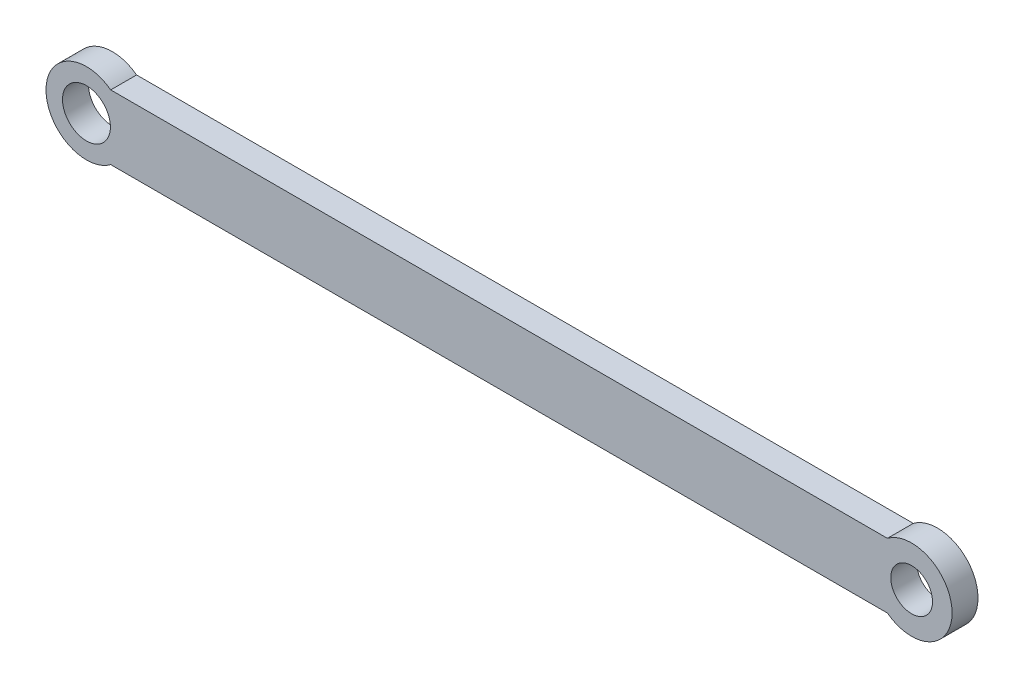
SolidWorks part; units mm, degrees
ref_plane "Front Plane" through (0, 0, 0) normal (0, 0, 1) x (1, 0, 0)
ref_plane "Top Plane" through (0, 0, 0) normal (0, 1, 0) x (1, 0, 0)
ref_plane "Right Plane" through (0, 0, 0) normal (1, 0, 0) x (0, 0, -1)
sketch "Sketch1" plane through (0, 0, 0) normal (0, 0, 1) x (1, 0, 0)
  line L1 (4.7625, 0) -> (157.1625, 0)
  line L3 (4.7625, 12.7) -> (157.1625, 12.7)
  arc A0 (4.7625, 12.7) -> (4.7625, 0) centre (0, 6.35) ccw
  arc A1 (157.1625, 0) -> (157.1625, 12.7) centre (161.925, 6.35) ccw
  dimension "D3" = 15.875
  dimension "D4" = 15.875
extrude "Boss-Extrude1" add sketch "Sketch1" along normal blind 5.08
sketch "Sketch2" plane through (0, 0, 0) normal (0, 0, -1) x (-1, 0, 0)
  circle A0 centre (-161.925, 6.35) radius 4.0958
  arc A1 (-157.1625, 12.7) -> (-157.1625, 0) centre (-161.925, 6.35) ccw construction
  circle A2 centre (0, 6.35) radius 4.699
  arc A3 (-4.7625, 0) -> (-4.7625, 12.7) centre (0, 6.35) ccw construction
  dimension "D1" = 9.398
  dimension "D2" = 8.1915
extrude "Cut-Extrude1" cut sketch "Sketch2" against normal up to surface (5.08 mm away) up to face at (80.9625, 6.35, 5.08)
